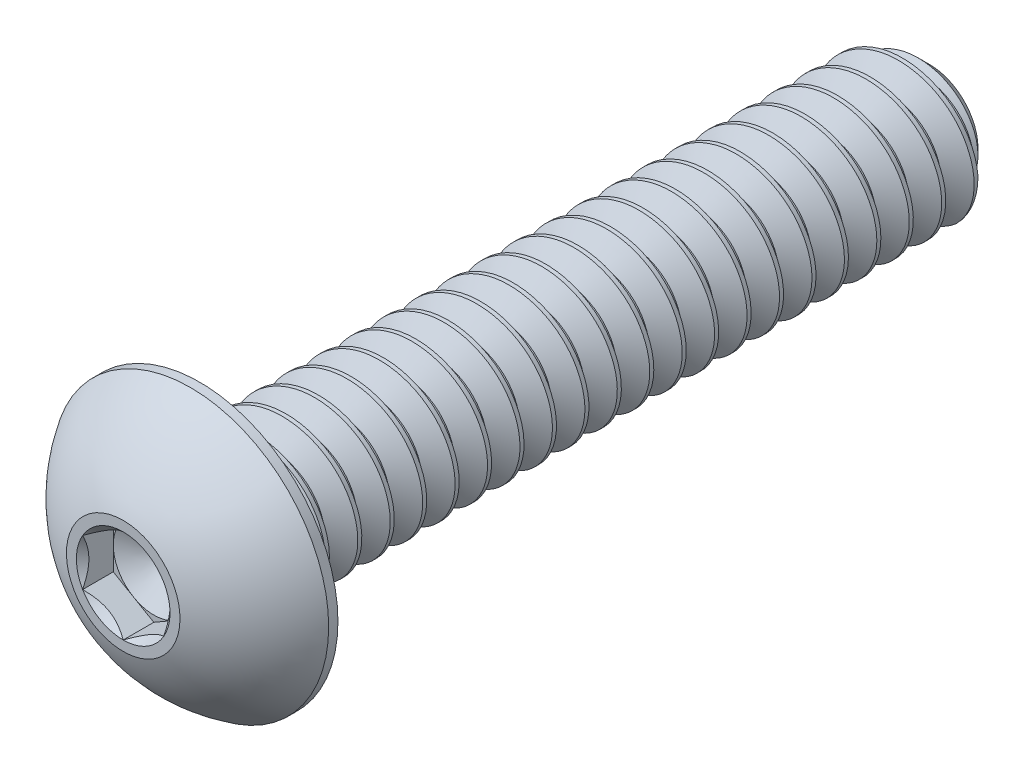
SolidWorks part; units mm, degrees
ref_plane "Front Plane" through (0, 0, 0) normal (0, 0, 1) x (1, 0, 0)
ref_plane "Top Plane" through (0, 0, 0) normal (0, 1, 0) x (1, 0, 0)
ref_plane "Right Plane" through (0, 0, 0) normal (1, 0, 0) x (0, 0, -1)
sketch "Sketch1" plane through (0, 0, 0) normal (1, 0, 0) x (0, 0, -1)
  line L0 (-7.893, 0) -> (7.893, 0) construction
  line L1 (-6.3944, 2.7051) -> (-6.3944, -2.7051) construction
  line L2 (-7.893, 0.7937) -> (-7.893, -0.7937) construction
  line L3 (7.893, 1.4224) -> (7.893, -1.4224) construction
  line L4 (7.8534, 1.4911) -> (8.1709, 0.9412) construction
  line L5 (8.1709, 0.9412) -> (8.4884, 1.4911) construction
  line L6 (8.4884, 1.4911) -> (7.8534, 1.4911) construction
  line L7 (8.1709, 1.4911) -> (8.1709, 1.4224) construction
  line L8 (8.1709, 0.9412) -> (8.1709, 1.01) construction
  line L9 (8.1312, 1.01) -> (8.2105, 1.01)
  line L10 (-7.893, 1.1113) -> (-7.893, -1.1113) construction
  line L11 (-6.3944, 2.7051) -> (-6.5759, 2.7051) construction
  line L12 (-7.893, 0.7937) -> (-7.2936, 0.7937) construction
  line L13 (-7.2936, 0.7937) -> (-6.8353, 0) construction
  point P5 (-6.3944, 0)
  point P10 (5.6705, -1.4224)
  dimension "Drive Size" = 1.5875
  dimension "Head Diameter" = 5.4102
  dimension "Head Height" = 1.4986
  dimension "Screw Size Decimal Equivalent" = 2.8448
  dimension "Length" = 14.2875
  dimension "D1" = 2.2225
  dimension "Pitch" = 0.635
  dimension "D2" = 0.0794
  dimension "D3" = 2.2225
  dimension "D4" = 0.1814
  dimension "D5" = 60
  dimension "D6" = 0.5994
sketch "Sketch2" plane through (0, 0, 0) normal (1, 0, 0) x (0, 0, -1)
  line L0 (-7.893, 0.7937) -> (-7.893, 1.1113)
  line L1 (-6.5759, 2.7051) -> (-6.3944, 2.7051)
  line L2 (-6.3944, 2.7051) -> (-6.3944, 1.4224)
  line L3 (-6.3944, 2.7051) -> (-6.3944, -2.7051) construction
  line L4 (-6.3944, 1.4224) -> (7.4168, 1.4224)
  line L5 (7.893, 0.9462) -> (7.893, 0)
  line L6 (-7.893, 0.7937) -> (-7.2936, 0.7937)
  line L7 (-7.2936, 0.7937) -> (-6.8353, 0)
  line L8 (7.893, 0) -> (-6.8353, 0)
  line L9 (7.4168, 1.4224) -> (7.893, 0.9462)
  line L10 (7.4168, -1.4224) -> (7.4168, 1.4224) construction
  arc A0 (-6.5759, 2.7051) -> (-7.893, 1.1113) centre (-4.9255, 0) ccw
  point P13 (7.893, 1.4224)
  point P25 (7.4168, 0)
  dimension "D1" = 0.4763
  dimension "D2" = 45
revolve "Revolve1" add sketch "Sketch2" angle 360 about L0
sketch "Sketch3" plane through (0, 0, 0) normal (0, 0, 1) x (1, 0, 0)
  line L1 (0, 0.9165) -> (-0.7938, 0.4583)
  line L2 (-0.7938, 0.4583) -> (-0.7937, -0.4583)
  line L3 (-0.7937, -0.4583) -> (0, -0.9165)
  line L4 (0, -0.9165) -> (0.7938, -0.4583)
  line L5 (0.7938, -0.4583) -> (0.7938, 0.4583)
  line L6 (0.7938, 0.4583) -> (0, 0.9165)
  circle A0 centre (0, 0) radius 0.7937 construction
extrude "Cut-Extrude1" cut sketch "Sketch3" along normal through all from vertex starting at point (0, 0.7937, 7.2936)
sketch "Sketch4" plane through (0, 0, 7.893) normal (0, 0, 1) x (1, 0, 0)
  circle A0 centre (0, 0) radius 0.9165
extrude "Cut-Extrude2" cut sketch "Sketch4" against normal up to next (15.7861 mm away) draft 45
sketch "Sketch9" plane through (0, 0, 0) normal (1, 0, 0) x (0, 0, -1)
  line L0 (7.893, -1.4224) -> (-6.3944, -1.4224) construction
  line L1 (-6.3944, -1.4224) -> (7.4168, -1.4224) construction
  line L2 (7.893, -0.9462) -> (7.893, 0.9462) construction
  line L3 (-6.3944, -1.4224) -> (-6.3944, 1.4224) construction
  point P9 (6.9405, -1.4224)
  dimension "D1" = 0.9525
sketch "Sketch5" plane through (0, 0, -7.893) normal (0, 0, -1) x (-1, 0, 0)
  circle A0 centre (0, 0) radius 1.4224
ref_axis "Center Axis1" through (0, 0, -89.0628) along (0, 0, 1)
ref_plane "Contact Plane1" through (0, 0, -7.893) normal (0, 0, 1) x (1, 0, 0)
ref_plane "Contact Plane2" through (0, 0, 6.3944) normal (0, 0, 1) x (1, 0, 0)
split "Split1" bodies to split 104 resulting bodies 109 110 split by face at (2.7051, 0, 6.3944)
curve "Helix/Spiral1" pitch 0.635 height 14.9225 radius 1.4224 centre (0, 0, -7.893) axis (0, 0, 1) start towards (0, 1, 0)
sketch "Sketch6" plane through (0, 0, 0) normal (1, 0, 0) x (0, 0, -1)
  line L0 (7.893, 1.4224) -> (8.4487, 1.4224)
  line L1 (8.4487, 1.4224) -> (8.2105, 1.01)
  line L2 (8.1312, 1.01) -> (8.2105, 1.01)
  line L3 (8.1312, 1.01) -> (7.893, 1.4224)
  line L4 (8.1709, 0.9412) -> (8.4884, 1.4911) construction
sweep "Cut-Sweep1" cut profiles "Sketch6" path "Helix/Spiral1" align with end faces yes
sketch "Sketch10" plane through (0, 0, 6.3944) normal (0, 0, -1) x (-1, 0, 0)
  circle A0 centre (0, 0) radius 1.4295
  dimension "D1" = 2.859
extrude "Boss-Extrude1" add sketch "Sketch10" along normal through all draft 30
equation "\"D2@Sketch1\"=\"Pitch@Sketch1\"*.125"
equation "\"D1@Sketch1\"=\"Pitch@Sketch1\"*3.5"
equation "\"D3@Sketch1\"=\"Drive Size@Sketch1\"*1.4"
equation "\"D4@Sketch1\"=(\"D3@Sketch1\"-\"Drive Size@Sketch1\")/3.5"
equation "\"D6@Sketch1\"=\"Head Height@Sketch1\"*.40"
equation "\"D1@Sketch2\"=\"Pitch@Sketch1\"*.750"
equation "\"D4@Helix/Spiral1\"=\"Pitch@Sketch1\""
equation "\"D3@Helix/Spiral1\" = \"D4@Helix/Spiral1\" + \"Length@Sketch1\""
equation "\"D1@Sketch9\"=\"Pitch@Sketch1\"*1.5"
equation "\"D1@Sketch10\"=\"Screw Size Decimal Equivalent@Sketch1\"*1.005"
